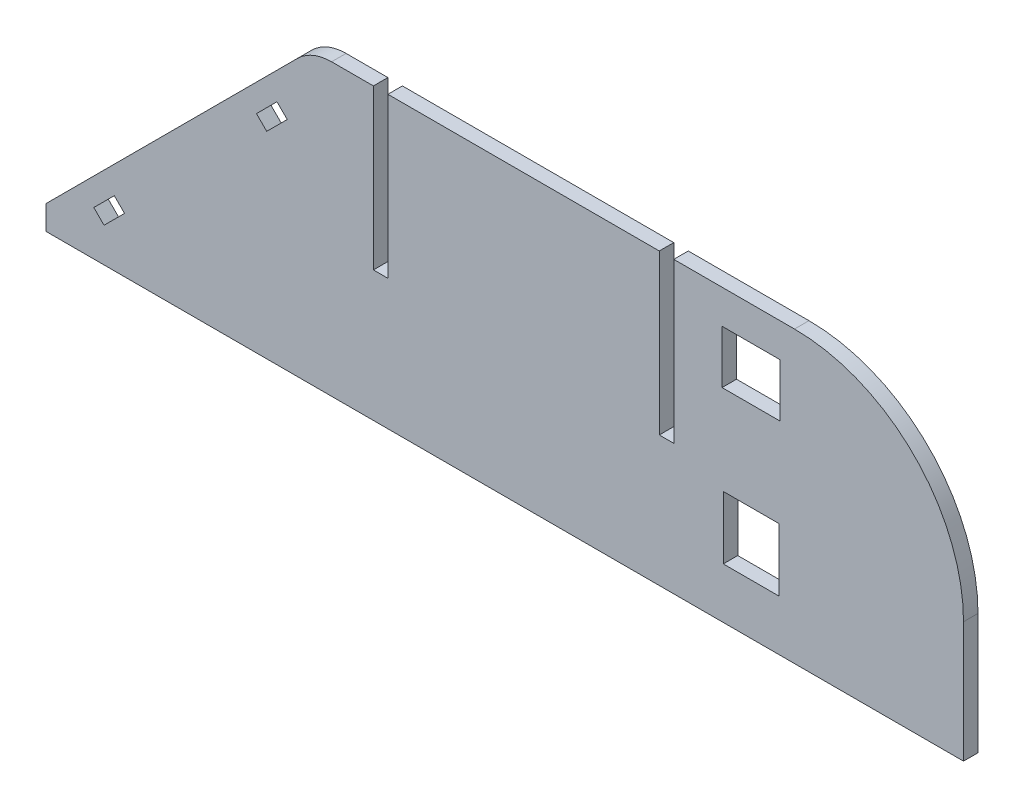
SolidWorks part; units mm, degrees
ref_plane "Alzado" through (0, 0, 0) normal (0, 0, 1) x (1, 0, 0)
ref_plane "Planta" through (0, 0, 0) normal (0, 1, 0) x (1, 0, 0)
ref_plane "Vista lateral" through (0, 0, 0) normal (1, 0, 0) x (0, 0, -1)
sketch "Croquis1" plane through (0, 0, 0) normal (0, 0, 1) x (1, 0, 0)
  line L0 (0, 30) -> (0, -30) construction
  line L1 (-95, 30) -> (95, 30)
  line L2 (-95, 30) -> (-95, -30)
  line L3 (-95, -30) -> (95, -30)
  line L4 (95, 30) -> (95, -30)
  line L5 (-95, 30) -> (95, -30) construction
  line L6 (-95, -30) -> (95, 30) construction
  line L7 (-40, 30) -> (-95, -25)
  line L10 (-21.5, -30) -> (-18.5, -30)
  line L11 (-21.5, 30) -> (-18.5, 30)
  point P0 (0, 0)
  point P8 (0, -22.5)
  point P13 (0, 22.5)
  dimension "D1" = 60
  dimension "D2" = 190
  dimension "D3" = 5
  dimension "D4" = 55
extrude "Saliente-Extruir1" add sketch "Croquis1" along normal blind 3 contours L3 L4 L1 L2 region at (11.7278, -1.7847, 0)
fillet "Redondeo1" radius 35 1 edges at (95, 30, 1.5)
sketch "Croquis2" plane through (0, 0, 3) normal (0, 0, 1) x (1, 0, 0)
  line L0 (-40, 30) -> (60, 30) construction
  line L1 (35, 30) -> (32, 30)
  line L2 (35, 30) -> (35, -3)
  line L3 (35, -3) -> (32, -3)
  line L4 (32, 30) -> (32, -3)
  line L5 (10, 30) -> (10, -30) construction
  line L6 (-27.2, 30) -> (-24.2, 30)
  line L7 (-27.2, 30) -> (-27.2, -3)
  line L8 (-27.2, -3) -> (-24.2, -3)
  line L9 (-24.2, 30) -> (-24.2, -3)
  line L10 (-95, -30) -> (95, -30) construction
  line L11 (95, -5) -> (95, -30) construction
  dimension "D1" = 33
  dimension "D2" = 33
  dimension "D3" = 3
  dimension "D4" = 3
  dimension "D5" = 56.2
  dimension "D6" = 60
extrude "Cortar-Extruir1" cut sketch "Croquis2" against normal through all
sketch "Croquis3" plane through (0, 0, 0) normal (0, 0, -1) x (-1, 0, 0)
  line L0 (95, -30) -> (-95, -30) construction
  line L1 (-56.75, -6.5) -> (-45.25, -6.5)
  line L2 (-56.75, -6.5) -> (-56.75, -19.5)
  line L3 (-56.75, -19.5) -> (-45.25, -19.5)
  line L4 (-45.25, -6.5) -> (-45.25, -19.5)
  line L5 (-56.75, -6.5) -> (-45.25, -19.5) construction
  line L6 (-56.75, -19.5) -> (-45.25, -6.5) construction
  line L7 (-95, -5) -> (-95, -30) construction
  point P0 (-51, -13)
  dimension "D1" = 11.5
  dimension "D2" = 13
  dimension "D3" = 10.5
  dimension "D4" = 44
extrude "Cortar-Extruir2" cut sketch "Croquis3" against normal through all
sketch "Croquis4" plane through (0, 0, 0) normal (0, 0, -1) x (-1, 0, 0)
  line L0 (-95, -5) -> (-95, -30) construction
  line L1 (-57, 23) -> (-45, 23)
  line L2 (-57, 23) -> (-57, 12)
  line L3 (-57, 12) -> (-45, 12)
  line L4 (-45, 23) -> (-45, 12)
  line L5 (-57, 23) -> (-45, 12) construction
  line L6 (-57, 12) -> (-45, 23) construction
  line L7 (-35, 30) -> (-60, 30) construction
  point P0 (-51, 17.5)
  dimension "D1" = 12
  dimension "D2" = 11
  dimension "D3" = 44
  dimension "D4" = 12.5
extrude "Cortar-Extruir3" cut sketch "Croquis4" against normal through all
fillet "Redondeo2" radius 10 1 edges at (-40, 30, 1.5)
sketch "Croquis5" plane through (0, 0, 0) normal (0, 0, -1) x (-1, 0, 0)
  line L0 (42.9289, 27.0711) -> (35.8759, 20.018) construction
  line L1 (47.1716, 17.1716) -> (45.0503, 15.0503)
  line L2 (45.0503, 15.0503) -> (49.2929, 10.8076)
  line L3 (49.2929, 10.8076) -> (51.4142, 12.9289)
  line L4 (51.4142, 12.9289) -> (47.1716, 17.1716)
  line L5 (95, -25) -> (90, -30) construction
  line L7 (85.1005, -20.7574) -> (82.9792, -22.8787)
  line L8 (82.9792, -22.8787) -> (78.7365, -18.636)
  line L9 (78.7365, -18.636) -> (80.8579, -16.5147)
  line L10 (80.8579, -16.5147) -> (85.1005, -20.7574)
  line L11 (42.9289, 27.0711) -> (95, -25) construction
  dimension "D1" = 6
  dimension "D2" = 3
  dimension "D3" = 10
  dimension "D4" = 4
  dimension "D5" = 3
  dimension "D6" = 6
  dimension "D7" = 10
  dimension "D8" = 4
extrude "Cortar-Extruir4" cut sketch "Croquis5" against normal through all
